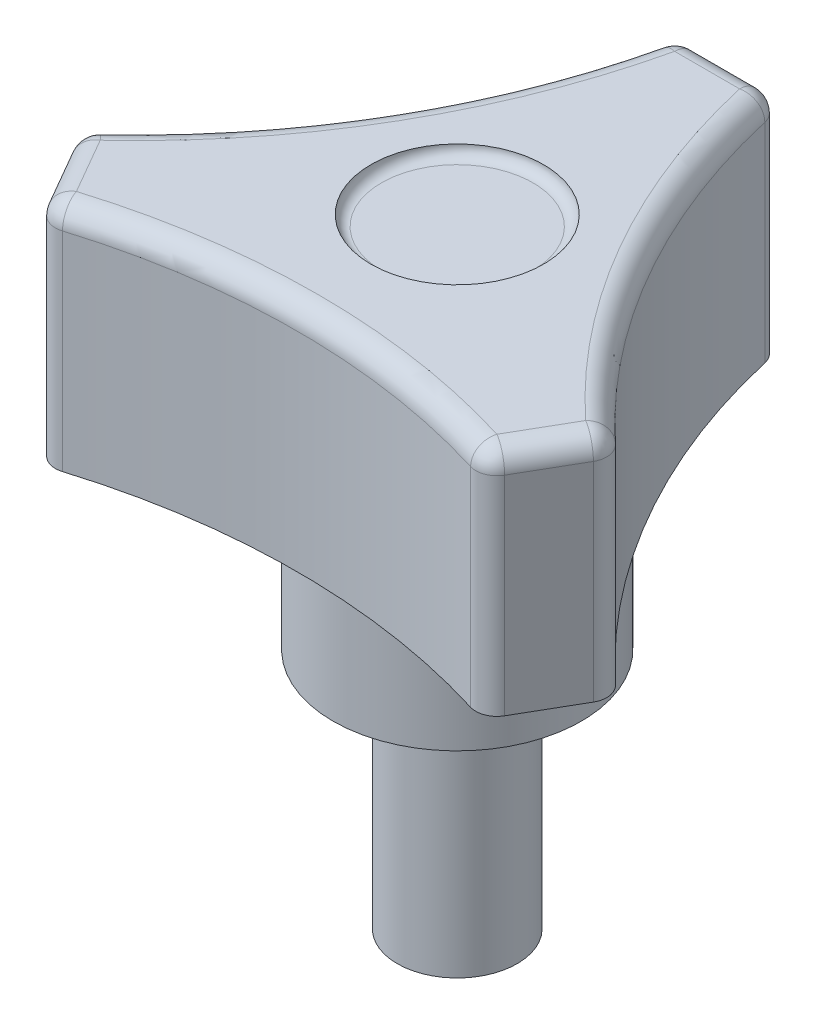
SolidWorks part; units mm, degrees
other "Bolt"
other "Knob Cap"
ref_plane "Front Plane" through (0, 0, 0) normal (0, 0, 1) x (1, 0, 0)
ref_plane "Top Plane" through (0, 0, 0) normal (0, 1, 0) x (1, 0, 0)
ref_plane "Right Plane" through (0, 0, 0) normal (1, 0, 0) x (0, 0, -1)
sketch "Sketch1" plane through (0, 0, 0) normal (0, 1, 0) x (1, 0, 0)
  circle A0 centre (0, 0) radius 2.85
  dimension "D1" = 5.7
extrude "Boss-Extrude1" add sketch "Sketch1" along normal blind 11.5
sketch "Sketch2" plane through (0, 11.5, 0) normal (0, 1, 0) x (1, 0, 0)
  circle A0 centre (0, 0) radius 5.9
  dimension "D1" = 11.8
extrude "Boss-Extrude2" add sketch "Sketch2" along normal blind 7 separate body
sketch "Sketch3" plane through (0, 18.5, 0) normal (0, 1, 0) x (1, 0, 0)
  line L0 (0, 0) -> (0, 12.6) construction
  line L1 (0, 0) -> (0, -7.6) construction
  line L2 (-10.45, -7.6) -> (10.45, -7.6) construction
  line L3 (-10.45, -7.6) -> (-10.45, -9.3) construction
  line L4 (10.45, -7.6) -> (10.45, -9.3) construction
  line L5 (10.45, -9.3) -> (-10.45, -9.3) construction
  line L6 (0, -7.6) -> (0, 12.6) construction
  line L7 (10.45, -9.3) -> (12.8, -5.2297)
  line L8 (-10.45, -9.3) -> (-12.8, -5.2297)
  line L9 (-2.35, 12.8703) -> (2.35, 12.8703)
  arc A0 (-10.45, -9.3) -> (10.45, -9.3) centre (0, -40.5684) cw
  circle A1 centre (0, 2.5) radius 2.5 construction
  arc A2 (-2.35, 12.8703) -> (-12.8, -5.2297) centre (-34.6542, 19.4545) cw
  arc A3 (12.8, -5.2297) -> (2.35, 12.8703) centre (34.6542, 19.4545) cw
  point P4 (0, 0)
  point P9 (0, -7.6)
  point P22 (0, -0.5531)
  dimension "D5" = 5
  dimension "D1" = 12.6
  dimension "D2" = 7.6
  dimension "D3" = 20.9
  dimension "D4" = 1.7
  dimension "D7" = 4.7
  dimension "D6" = 3
extrude "Boss-Extrude3" add sketch "Sketch3" along normal blind 10.9
fillet "Fillet1" radius 1 12 edges at (12.8, 23.95, 5.2297) (2.35, 23.95, -12.8703) (0, 29.4, -12.8703) (-2.35, 23.95, -12.8703) (-12.8, 23.95, 5.2297) (-10.45, 23.95, 9.3) (10.45, 23.95, 9.3) (-11.625, 29.4, 7.2648) (11.625, 29.4, 7.2648) (-6.1028, 29.4, -2.9703) (6.1028, 29.4, -2.9703) (0, 29.4, 7.6)
sketch "Sketch4" plane through (0, 29.4, 0) normal (0, 1, 0) x (1, 0, 0)
  circle A0 centre (0, 0) radius 4.1
  circle A1 centre (0, 0) radius 5.9
  circle A2 centre (0, 0) radius 5.9 construction
  dimension "D2" = 8.2
  dimension "D1" = 0
extrude "Cut-Extrude1" cut sketch "Sketch4" against normal blind 0.5
fillet "Fillet2" radius 0.5 1 edges at (0, 28.9, 4.1)
